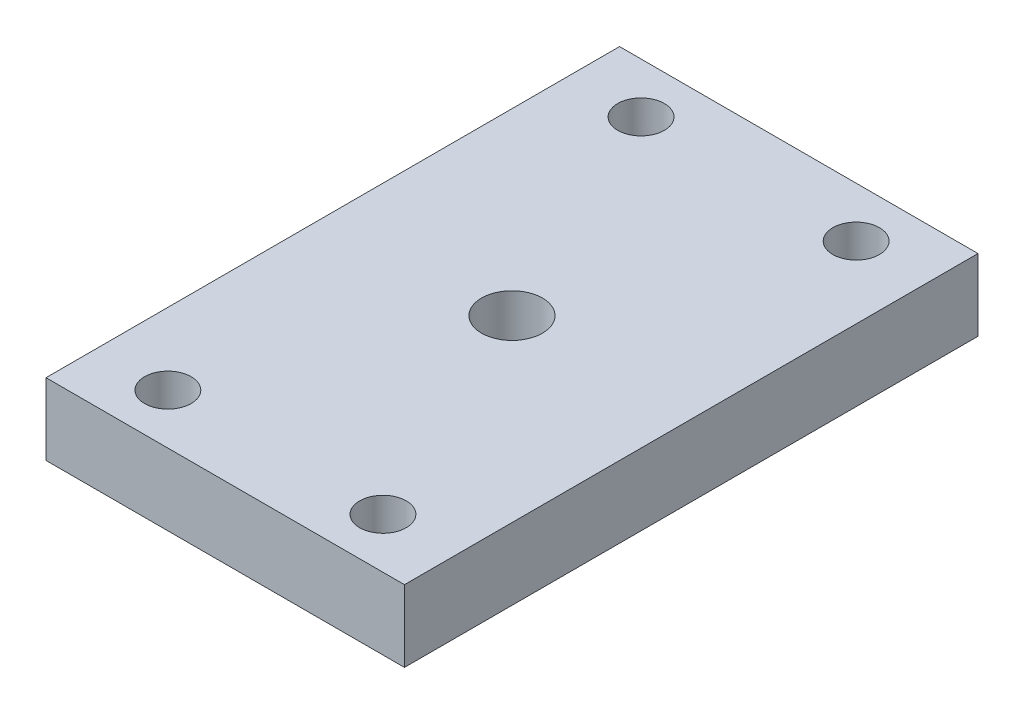
SolidWorks part; units mm, degrees
ref_plane "Front Plane" through (0, 0, 0) normal (0, 0, 1) x (1, 0, 0)
ref_plane "Top Plane" through (0, 0, 0) normal (0, 1, 0) x (1, 0, 0)
ref_plane "Right Plane" through (0, 0, 0) normal (1, 0, 0) x (0, 0, -1)
sketch "Sketch1" plane through (0, 0, 0) normal (0, 1, 0) x (1, 0, 0)
  line L0 (30.8021, -28.7414) -> (-19.1979, -28.7414) construction
  line L5 (-19.0216, -6.7414) -> (30.8021, -6.7414) construction
  line L6 (-19.1097, -46.7414) -> (30.8903, -46.7414)
  line L7 (30.8021, 15.2586) -> (-19.0216, 15.2586) construction
  line L8 (30.8021, 15.2586) -> (30.8021, -28.7414) construction
  line L9 (30.8021, -28.7414) -> (-19.0216, -28.7414) construction
  line L10 (-19.0216, 15.2586) -> (-19.0216, -28.7414) construction
  line L11 (-19.0216, 15.2586) -> (30.8021, -28.7414) construction
  line L12 (-19.0216, -28.7414) -> (30.8021, 15.2586) construction
  line L13 (-19.1097, -46.7414) -> (-19.1097, 33.2586)
  line L14 (-19.1097, 33.2586) -> (30.8903, 33.2586)
  line L15 (30.8903, -46.7414) -> (30.8903, 33.2586)
  line L16 (-19.1097, -46.7414) -> (30.8903, 33.2586) construction
  line L17 (-19.1097, 33.2586) -> (30.8903, -46.7414) construction
  point P0 (0, 0)
  point P1 (5.8903, -6.7414)
  dimension "D1" = 80
  dimension "D2" = 50
extrude "Boss-Extrude1" add sketch "Sketch1" along normal blind 10
sketch "Sketch2" plane through (0, 0, 0) normal (0, -1, 0) x (1, 0, 0)
  line L0 (5.8903, -33.2586) -> (5.8903, 46.7414) construction
  line L1 (30.8903, -33.2586) -> (-19.1097, -33.2586) construction
  line L2 (-19.1097, 46.7414) -> (30.8903, 46.7414) construction
  circle A0 centre (5.8903, 6.7414) radius 4.25
  dimension "D1" = 8.5
extrude "Cut-Extrude1" cut sketch "Sketch2" against normal up to next
sketch "Sketch5" plane through (0, 10, 0) normal (0, 1, 0) x (1, 0, 0)
  line L0 (-19.1097, -39.7414) -> (30.8903, -39.7414) construction
  line L1 (-19.1097, 33.2586) -> (-19.1097, -46.7414) construction
  line L2 (30.8903, -46.7414) -> (30.8903, 33.2586) construction
  line L3 (-19.1097, 26.2586) -> (30.8903, 26.2586) construction
  line L4 (-19.1097, -46.7414) -> (30.8903, -46.7414) construction
  line L5 (30.8903, 33.2586) -> (-19.1097, 33.2586) construction
  circle A0 centre (-9.1097, -39.7414) radius 3.25
  circle A1 centre (20.8903, -39.7414) radius 3.25
  circle A2 centre (-9.1097, 26.2586) radius 3.25
  circle A3 centre (20.8903, 26.2586) radius 3.25
  dimension "D3" = 6.5
  dimension "D4" = 6.5
  dimension "D5" = 6.5
  dimension "D6" = 6.5
  dimension "D1" = 7
  dimension "D2" = 7
  dimension "D7" = 10
  dimension "D8" = 10
  dimension "D9" = 10
  dimension "D10" = 10
extrude "Cut-Extrude3" cut sketch "Sketch5" against normal up to next
